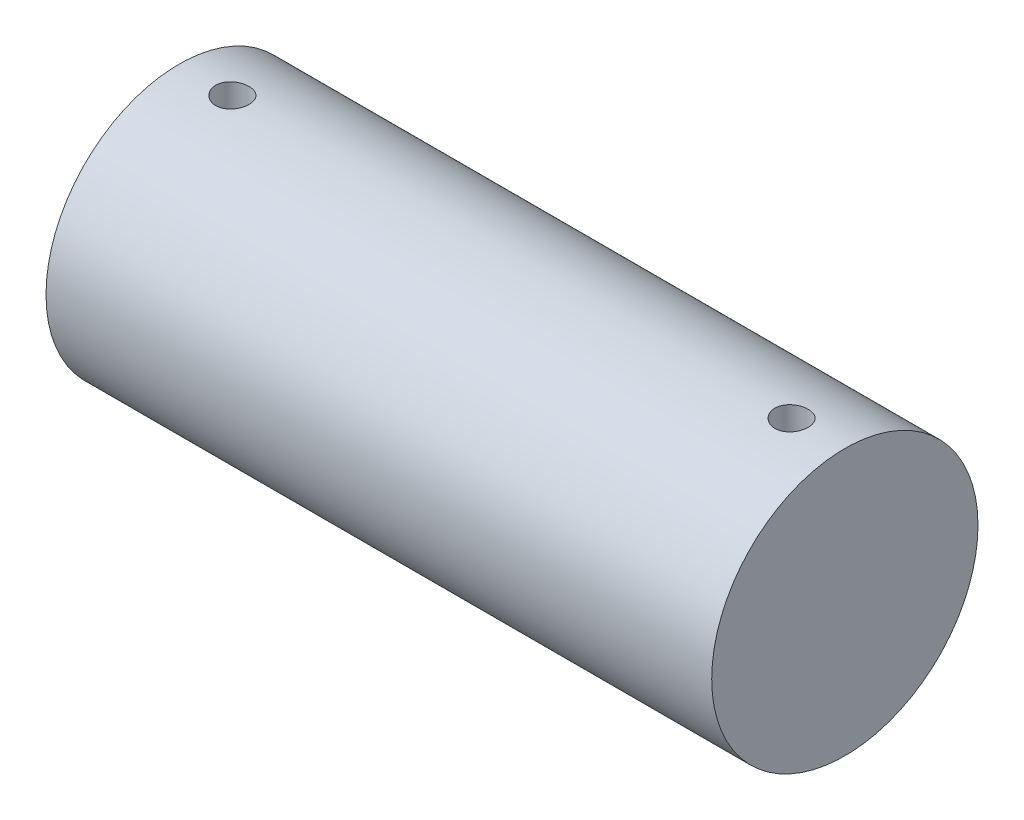
SolidWorks part; units mm, degrees
ref_plane "Ön Düzlem" through (0, 0, 0) normal (0, 0, 1) x (1, 0, 0)
ref_plane "Üst Düzlem" through (0, 0, 0) normal (0, 1, 0) x (1, 0, 0)
ref_plane "Sağ Düzlem" through (0, 0, 0) normal (1, 0, 0) x (0, 0, -1)
sketch "Çizim1" plane through (0, 0, 0) normal (1, 0, 0) x (0, 0, -1)
  circle A0 centre (0, 0) radius 2
  dimension "D1" = 4
extrude "Yükseklik-Ekstrüzyon1" add sketch "Çizim1" along normal blind 10
sketch "Çizim2" plane through (0, 0, 0) normal (0, 1, 0) x (1, 0, 0)
  line L0 (0.8, 0) -> (1.05, 0) construction
  line L2 (8.95, 0) -> (9.2, 0) construction
  circle A1 centre (0.8, 0) radius 0.25
  circle A2 centre (9.2, 0) radius 0.25
  dimension "D2" = 0.5
  dimension "D3" = 0.5
extrude "Kes-Ekstrüzyon1" cut sketch "Çizim2" against normal blind 10 and the other way blind 10
scale "Ölçek1" scale about centroid uniform scaling yes scale factor 0.5
